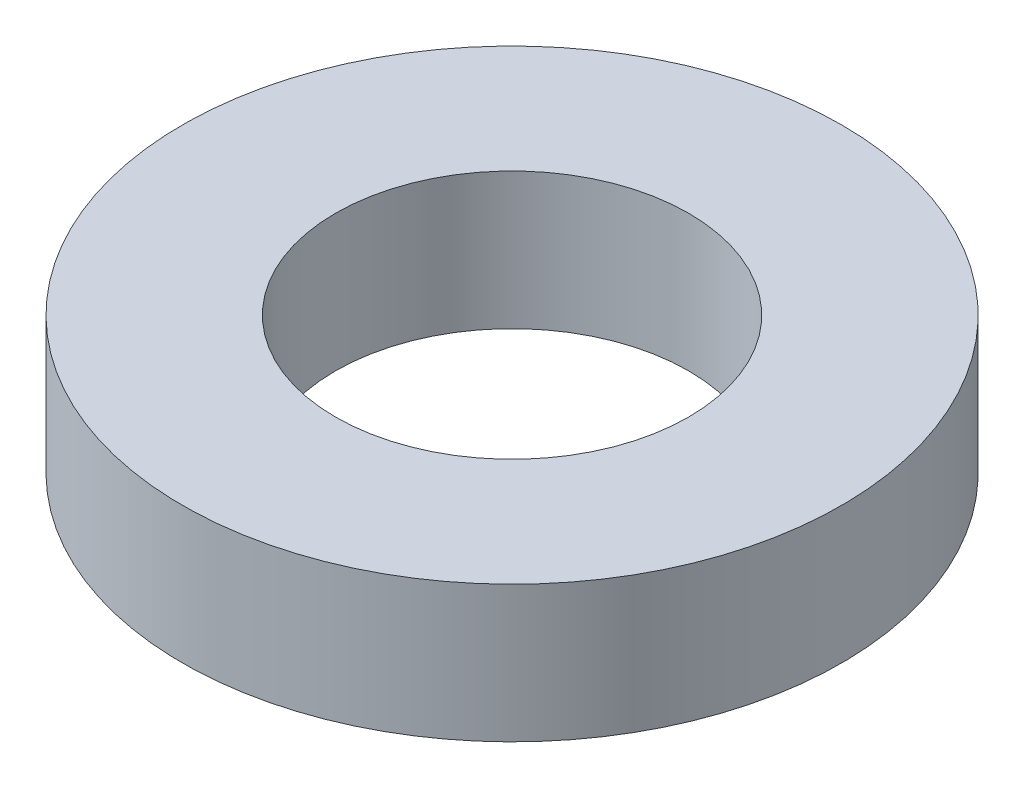
SolidWorks part; units mm, degrees
ref_plane "Front Plane" through (0, 0, 0) normal (0, 0, 1) x (1, 0, 0)
ref_plane "Top Plane" through (0, 0, 0) normal (0, 1, 0) x (1, 0, 0)
ref_plane "Right Plane" through (0, 0, 0) normal (1, 0, 0) x (0, 0, -1)
sketch "Sketch1" plane through (0, 0, 0) normal (0, 1, 0) x (1, 0, 0)
  circle A0 centre (0, 0) radius 70
  dimension "FLANGE_OD" = 140
extrude "Boss-Extrude1" add sketch "Sketch1" along normal blind 29
sketch "Sketch2" plane through (0, 0, 0) normal (0, 1, 0) x (1, 0, 0)
  circle A0 centre (0, 0) radius 37.5
  dimension "BORE_D" = 75
extrude "Cut-Extrude1" cut sketch "Sketch2" along normal through all
sketch "Sketch3" plane through (0, 29, 0) normal (0, 1, 0) x (1, 0, 0)
  circle A0 centre (0, 0) radius 28.42 construction
  circle A1 centre (-28.42, 0) radius 5.3655
  dimension "BOLT_D" = 10.731
  dimension "BOLT_PCD" = 56.8399
extrude "Cut-Extrude2" cut sketch "Sketch3" against normal blind 17.7056 rebuild error yes
pattern_circular "CirPattern1" count 8 over 360 rebuild error yes
